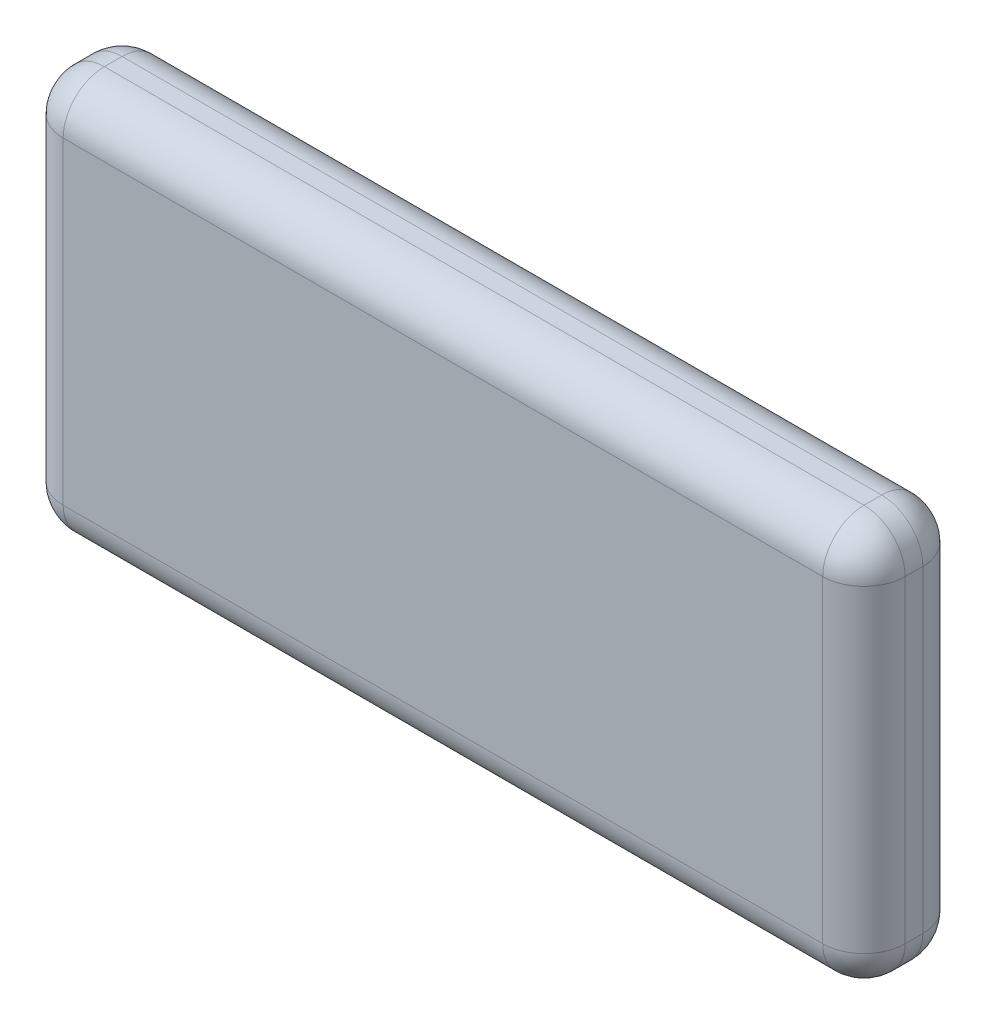
SolidWorks part; units mm, degrees
ref_plane "Front Plane" through (0, 0, 0) normal (0, 0, 1) x (1, 0, 0)
ref_plane "Top Plane" through (0, 0, 0) normal (0, 1, 0) x (1, 0, 0)
ref_plane "Right Plane" through (0, 0, 0) normal (1, 0, 0) x (0, 0, -1)
sketch "Sketch1" plane through (0, 0, 0) normal (0, 0, 1) x (1, 0, 0)
  line L1 (-137.2035, 47.6903) -> (5.7965, 47.6903)
  line L2 (-137.2035, 47.6903) -> (-137.2035, -20.3097)
  line L3 (-137.2035, -20.3097) -> (5.7965, -20.3097)
  line L4 (5.7965, 47.6903) -> (5.7965, -20.3097)
  dimension "D1" = 68
  dimension "D2" = 143
extrude "Boss-Extrude1" add sketch "Sketch1" along normal blind 17
fillet "Fillet1" radius 7 10 edges at (5.7965, 47.6903, 8.5) (-65.7035, 47.6903, 17) (-137.2035, 47.6903, 8.5) (-65.7035, 47.6903, 0) (5.7965, 13.6903, 17) (5.7965, 13.6903, 0) (-137.2035, 13.6903, 17) (-137.2035, 13.6903, 0) (-65.7035, -20.3097, 17) (-65.7035, -20.3097, 0)
fillet "Fillet2" radius 7 6 edges at (-135.1533, -18.2595, 14.9497) (-137.2035, -20.3097, 8.5) (3.7462, -18.2595, 14.9497) (5.7965, -20.3097, 8.5) (-135.1533, -18.2595, 2.0503) (3.7462, -18.2595, 2.0503)
